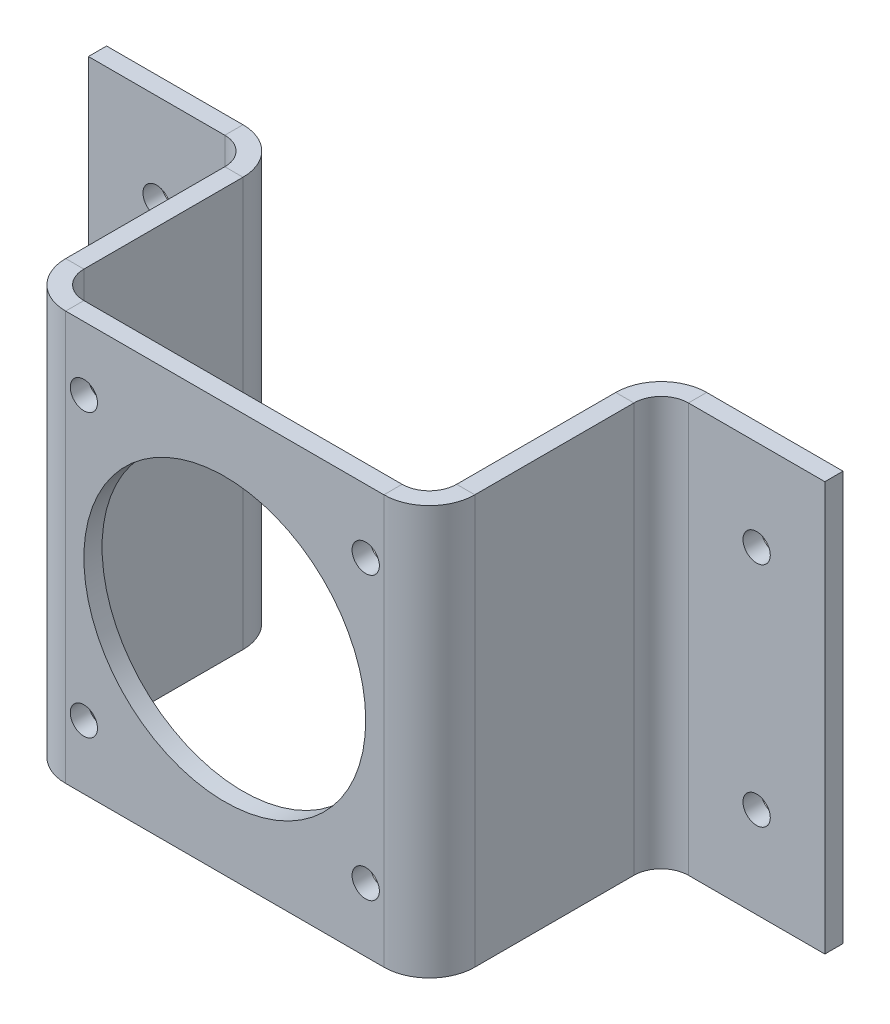
SolidWorks part; units mm, degrees
note: The reader was unsure of these and kept them because the rebuilt part matched: flange length of "Edge-Flange1", "Edge-Flange2", "Edge-Flange3", "Edge-Flange4".
ref_plane "Front Plane" through (0, 0, 0) normal (0, 0, 1) x (1, 0, 0)
ref_plane "Top Plane" through (0, 0, 0) normal (0, 1, 0) x (1, 0, 0)
ref_plane "Right Plane" through (0, 0, 0) normal (1, 0, 0) x (0, 0, -1)
sketch "Sketch1" plane through (0, 0, 0) normal (0, 0, 1) x (1, 0, 0)
  line L0 (-15.5, 15.5) -> (-15.5, -15.5) construction
  line L1 (-22.5, -22.5) -> (22.5, -22.5)
  line L2 (-22.5, -22.5) -> (-22.5, 22.5)
  line L3 (-22.5, 22.5) -> (22.5, 22.5)
  line L4 (22.5, -22.5) -> (22.5, 22.5)
  line L5 (-15.5, -15.5) -> (15.5, -15.5) construction
  line L6 (15.5, -15.5) -> (15.5, 15.5) construction
  line L7 (15.5, 15.5) -> (-15.5, 15.5) construction
  circle A0 centre (0, 0) radius 15.5
  circle A1 centre (-15.5, 15.5) radius 1.5
  circle A2 centre (15.5, 15.5) radius 1.5
  circle A3 centre (15.5, -15.5) radius 1.5
  circle A4 centre (-15.5, -15.5) radius 1.5
  point P4 (17.2113, 15.6115)
  point P10 (0, 22.5)
  point P11 (22.5, 0)
  point P18 (15.3715, 15.8653)
  point P19 (16.0109, 16.0109)
  point P20 (16.0109, 16.0109)
  point P21 (0, 15.5)
  point P22 (15.5, 0)
  dimension "D3" = 31
  dimension "D5" = 3
  dimension "D1" = 45
  dimension "D2" = 45
  dimension "D4" = 31
base flange "Base-Flange1" sketch "Sketch1" thickness 2 reverse thickness direction no parameters "D1"=3
edge flange "Edge-Flange1" sketch "Sketch8" flange angle 90 flange length 27.5 flange position material inside bend radius 3 thickness 2 relief rectangular parameters "D6"=10
sketch "Sketch8" plane through (22.5, 0, -2) normal (1, 0, 0) x (0, -1, 0)
  line L2 (-22.5, 0) -> (-22.5, 25.5)
  line L3 (-22.5, 25.5) -> (22.5, 25.5)
  line L4 (22.5, 25.5) -> (22.5, 0)
  line L7 (22.5, 0) -> (-22.5, 0) construction
  line L8 (22.5, 0) -> (-22.5, 0)
bend "EdgeBend1" bend radius 3 bend angle 90 parameters "D5"=1
edge flange "Edge-Flange2" sketch "Sketch11" flange angle 90 flange length 20 flange position material inside bend radius 3 thickness 2 relief rectangular parameters "D6"=10
sketch "Sketch11" plane through (22.5, 0, -27.5) normal (0, 0, -1) x (0, 1, 0)
  line L2 (-22.5, 0) -> (-22.5, 18)
  line L3 (-22.5, 18) -> (22.5, 18)
  line L4 (22.5, 18) -> (22.5, 0)
  line L7 (-22.5, 0) -> (22.5, 0) construction
  line L8 (-22.5, 0) -> (22.5, 0)
bend "EdgeBend2" bend radius 3 bend angle 90 parameters "D5"=2
edge flange "Edge-Flange3" sketch "Sketch14" flange angle 90 flange length 27.5 flange position material inside bend radius 3 thickness 2 relief rectangular parameters "D6"=10
sketch "Sketch14" plane through (-22.5, 0, -2) normal (-1, 0, 0) x (0, 1, 0)
  line L0 (22.5, 0) -> (-22.5, 0) construction
  line L1 (22.5, 0) -> (-22.5, 0)
  line L2 (-22.5, 0) -> (-22.5, 25.5)
  line L3 (-22.5, 25.5) -> (22.5, 25.5)
  line L4 (22.5, 25.5) -> (22.5, 0)
bend "EdgeBend3" bend radius 3 bend angle 90 parameters "D5"=3
edge flange "Edge-Flange4" sketch "Sketch17" flange angle 90 flange length 20 flange position material inside bend radius 3 thickness 2 relief rectangular parameters "D6"=10
sketch "Sketch17" plane through (-22.5, 0, -27.5) normal (0, 0, -1) x (0, -1, 0)
  line L0 (-22.5, 0) -> (22.5, 0) construction
  line L1 (-22.5, 0) -> (22.5, 0)
  line L2 (-22.5, 0) -> (-22.5, 18)
  line L3 (-22.5, 18) -> (22.5, 18)
  line L4 (22.5, 18) -> (22.5, 0)
bend "EdgeBend4" bend radius 3 bend angle 90 parameters "D5"=4
sketch "Sketch18" plane through (0, 0, -25.5) normal (0, 0, 1) x (1, 0, 0)
  line L0 (-40.5, 22.5) -> (-25.5, 22.5) construction
  line L1 (-25.5, -22.5) -> (-40.5, -22.5) construction
  circle A0 centre (-33, 12.5) radius 1.5
  circle A1 centre (-33, -12.5) radius 1.5
  point P4 (0, 0)
  point P7 (-33, 22.5)
  dimension "D1" = 3
  dimension "D2" = 10
  dimension "D3" = 10
sketch "Sketch19" plane through (0, 0, -25.5) normal (0, 0, 1) x (1, 0, 0)
  line L2 (25.5, 22.5) -> (40.5, 22.5) construction
  line L3 (40.5, -22.5) -> (25.5, -22.5) construction
  circle A0 centre (33, 12.5) radius 1.5
  circle A1 centre (33, -12.5) radius 1.5
  point P4 (0, 0)
  point P5 (0, 0)
  point P6 (0, 0)
  point P9 (33, 22.5)
  dimension "D1" = 3
  dimension "D2" = 10
  dimension "D3" = 10
extrude "Cut-Extrude1" cut sketch "Sketch18" against normal blind 10 normal cut yes
extrude "Cut-Extrude2" cut sketch "Sketch19" against normal blind 10 normal cut yes
sketch "Bend-Lines1" [suppressed] plane through (0, 0, 0) normal (0, 1, 0) x (1, 0, 0)
sketch "Bounding-Box1" [suppressed] plane through (0, 0, 0) normal (0, 1, 0) x (1, 0, 0)
sheet metal parameters "Sheet-Metal1" thickness 2 parameters "D1"=3
flat pattern "Flat-Pattern1" [suppressed]
sketch "Bend-Lines2" plane through (0, 0, 0) normal (0, 1, 0) x (1, 0, 0)
sketch3d "Bounding-Box2" [suppressed]
  line L0 (22.5, -22.5, 0) -> (-22.5, -22.5, 0) construction
  line L1 (22.5, 22.5, 0) -> (-22.5, 22.5, 0) construction
  line L2 (22.5, -22.5, 0) -> (22.5, 22.5, 0) construction
  line L3 (-22.5, -22.5, 0) -> (-22.5, 22.5, 0) construction
sheet metal parameters "Sheet-Metal2" thickness 2 parameters "D1"=3
flat pattern "Flat-Pattern1"
sketch "Bend-Lines2" plane through (0, 0, 0) normal (0, 0, 1) x (1, 0, 0)
  line L0 (20.6416, -22.5) -> (20.6416, 22.5) construction
  line L1 (20.6416, -22.5) -> (20.6416, 22.5) construction
sketch3d "Bounding-Box2" [suppressed]
  line L0 (-22.5, -22.5, 0) -> (46.2832, -22.5, 0) construction
  line L1 (-22.5, 22.5, 0) -> (46.2832, 22.5, 0) construction
  line L2 (-22.5, -22.5, 0) -> (-22.5, 22.5, 0) construction
  line L3 (46.2832, -22.5, 0) -> (46.2832, 22.5, 0) construction
bend of the flat pattern "Flatten-<EdgeBend1>1"
sheet metal parameters "Sheet-Metal3" thickness 2 parameters "D1"=3
flat pattern "Flat-Pattern1"
sketch "Bend-Lines2" plane through (0, 0, 0) normal (0, 0, 1) x (1, 0, 0)
  line L0 (20.6416, -22.5) -> (20.6416, 22.5) construction
  line L1 (20.6416, -22.5) -> (20.6416, 22.5) construction
  line L2 (44.4248, -22.5) -> (44.4248, 22.5) construction
  line L3 (44.4248, -22.5) -> (44.4248, 22.5) construction
sketch3d "Bounding-Box2" [suppressed]
  line L0 (-22.5, -22.5, 0) -> (62.5664, -22.5, 0) construction
  line L1 (-22.5, 22.5, 0) -> (62.5664, 22.5, 0) construction
  line L2 (-22.5, -22.5, 0) -> (-22.5, 22.5, 0) construction
  line L3 (62.5664, -22.5, 0) -> (62.5664, 22.5, 0) construction
bend of the flat pattern "Flatten-<EdgeBend1>1"
bend of the flat pattern "Flatten-<EdgeBend2>1"
sheet metal parameters "Sheet-Metal4" thickness 2 parameters "D1"=3
flat pattern "Flat-Pattern1"
sketch "Bend-Lines2" plane through (0, 0, 0) normal (0, 0, 1) x (1, 0, 0)
  line L0 (20.6416, -22.5) -> (20.6416, 22.5) construction
  line L1 (20.6416, -22.5) -> (20.6416, 22.5) construction
  line L2 (44.4248, -22.5) -> (44.4248, 22.5) construction
  line L3 (44.4248, -22.5) -> (44.4248, 22.5) construction
  line L4 (-20.6416, 22.5) -> (-20.6416, -22.5) construction
  line L5 (-20.6416, 22.5) -> (-20.6416, -22.5) construction
sketch3d "Bounding-Box2" [suppressed]
  line L0 (-46.2832, -22.5, 0) -> (62.5664, -22.5, 0) construction
  line L1 (-46.2832, 22.5, 0) -> (62.5664, 22.5, 0) construction
  line L2 (-46.2832, -22.5, 0) -> (-46.2832, 22.5, 0) construction
  line L3 (62.5664, -22.5, 0) -> (62.5664, 22.5, 0) construction
bend of the flat pattern "Flatten-<EdgeBend1>1"
bend of the flat pattern "Flatten-<EdgeBend2>1"
bend of the flat pattern "Flatten-<EdgeBend3>1"
sheet metal parameters "Sheet-Metal5" thickness 2 parameters "D1"=3
flat pattern "Flat-Pattern1"
sketch "Bend-Lines2" plane through (0, 0, 0) normal (0, 0, 1) x (1, 0, 0)
  line L0 (20.6416, -22.5) -> (20.6416, 22.5) construction
  line L1 (20.6416, -22.5) -> (20.6416, 22.5) construction
  line L2 (44.4248, -22.5) -> (44.4248, 22.5) construction
  line L3 (44.4248, -22.5) -> (44.4248, 22.5) construction
  line L4 (-20.6416, 22.5) -> (-20.6416, -22.5) construction
  line L5 (-20.6416, 22.5) -> (-20.6416, -22.5) construction
  line L6 (-44.4248, 22.5) -> (-44.4248, -22.5) construction
  line L7 (-44.4248, 22.5) -> (-44.4248, -22.5) construction
sketch3d "Bounding-Box2" [suppressed]
  line L0 (-62.5664, -22.5, 0) -> (62.5664, -22.5, 0) construction
  line L1 (-62.5664, 22.5, 0) -> (62.5664, 22.5, 0) construction
  line L2 (-62.5664, -22.5, 0) -> (-62.5664, 22.5, 0) construction
  line L3 (62.5664, -22.5, 0) -> (62.5664, 22.5, 0) construction
bend of the flat pattern "Flatten-<EdgeBend1>1"
bend of the flat pattern "Flatten-<EdgeBend2>1"
bend of the flat pattern "Flatten-<EdgeBend3>1"
bend of the flat pattern "Flatten-<EdgeBend4>1"
sheet metal parameters "Sheet-Metal6" thickness 2 parameters "D1"=3
flat pattern "Flat-Pattern1" [suppressed]
sketch "Bend-Lines2" plane through (0, 0, 0) normal (0, 0, 1) x (1, 0, 0)
  line L0 (20.6416, -22.5) -> (20.6416, 22.5) construction
  line L1 (20.6416, -22.5) -> (20.6416, 22.5) construction
  line L2 (44.4248, -22.5) -> (44.4248, 22.5) construction
  line L3 (44.4248, -22.5) -> (44.4248, 22.5) construction
  line L4 (-20.6416, 22.5) -> (-20.6416, -22.5) construction
  line L5 (-20.6416, 22.5) -> (-20.6416, -22.5) construction
  line L6 (-44.4248, 22.5) -> (-44.4248, -22.5) construction
  line L7 (-44.4248, 22.5) -> (-44.4248, -22.5) construction
sketch3d "Bounding-Box2" [suppressed]
  line L0 (-62.5664, -22.5, 0) -> (62.5664, -22.5, 0) construction
  line L1 (-62.5664, 22.5, 0) -> (62.5664, 22.5, 0) construction
  line L2 (-62.5664, -22.5, 0) -> (-62.5664, 22.5, 0) construction
  line L3 (62.5664, -22.5, 0) -> (62.5664, 22.5, 0) construction
bend of the flat pattern "Flatten-<EdgeBend1>1"
bend of the flat pattern "Flatten-<EdgeBend2>1"
bend of the flat pattern "Flatten-<EdgeBend3>1"
bend of the flat pattern "Flatten-<EdgeBend4>1"
sketch "Sketch19-1" [suppressed] plane through (22.0664, 0, 0) normal (0, 0, 1) x (1, 0, 0)
  line L2 (-84.6327, 22.5) -> (-69.6327, 22.5) construction
  line L3 (40.5, -22.5) -> (-84.6327, -22.5) construction
  circle A0 centre (33, 12.5) radius 1.5
  circle A1 centre (33, -12.5) radius 1.5
  dimension "D1" = 3
  dimension "D2" = 10
  dimension "D3" = 10
sheet metal parameters "Sheet-Metal7" thickness 2 parameters "D1"=3
flat pattern "Flat-Pattern1" [suppressed]
sketch "Bend-Lines2" plane through (0, 0, 0) normal (0, 0, 1) x (1, 0, 0)
  line L0 (20.6416, -22.5) -> (20.6416, 22.5) construction
  line L1 (20.6416, -22.5) -> (20.6416, 22.5) construction
  line L2 (44.4248, -22.5) -> (44.4248, 22.5) construction
  line L3 (44.4248, -22.5) -> (44.4248, 22.5) construction
  line L4 (-20.6416, 22.5) -> (-20.6416, -22.5) construction
  line L5 (-20.6416, 22.5) -> (-20.6416, -22.5) construction
  line L6 (-44.4248, 22.5) -> (-44.4248, -22.5) construction
  line L7 (-44.4248, 22.5) -> (-44.4248, -22.5) construction
sketch3d "Bounding-Box2" [suppressed]
  line L0 (-62.5664, -22.5, 0) -> (62.5664, -22.5, 0) construction
  line L1 (-62.5664, 22.5, 0) -> (62.5664, 22.5, 0) construction
  line L2 (-62.5664, -22.5, 0) -> (-62.5664, 22.5, 0) construction
  line L3 (62.5664, -22.5, 0) -> (62.5664, 22.5, 0) construction
bend of the flat pattern "Flatten-<EdgeBend1>1"
bend of the flat pattern "Flatten-<EdgeBend2>1"
bend of the flat pattern "Flatten-<EdgeBend3>1"
bend of the flat pattern "Flatten-<EdgeBend4>1"
sketch "Sketch19-1" [suppressed] plane through (22.0664, 0, 0) normal (0, 0, 1) x (1, 0, 0)
  line L2 (-84.6327, 22.5) -> (-69.6327, 22.5) construction
  line L3 (40.5, -22.5) -> (-84.6327, -22.5) construction
  circle A0 centre (33, 12.5) radius 1.5
  circle A1 centre (33, -12.5) radius 1.5
  dimension "D1" = 3
  dimension "D2" = 10
  dimension "D3" = 10
